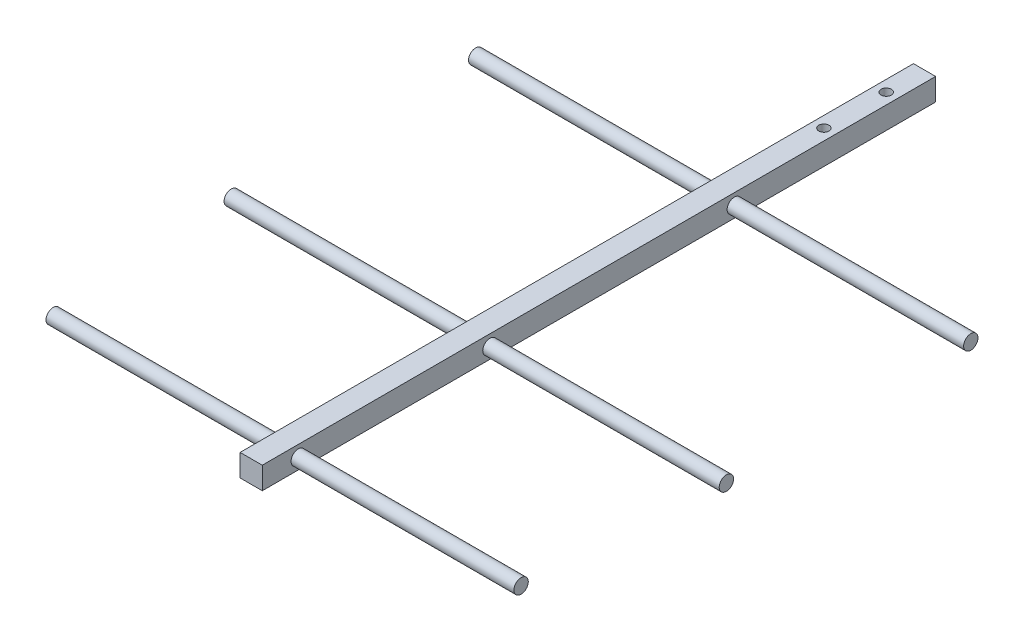
SolidWorks part; units mm, degrees
ref_plane "Front Plane" through (0, 0, 0) normal (0, 0, 1) x (1, 0, 0)
ref_plane "Top Plane" through (0, 0, 0) normal (0, 1, 0) x (1, 0, 0)
ref_plane "Right Plane" through (0, 0, 0) normal (1, 0, 0) x (0, 0, -1)
sketch "Sketch1" plane through (0, 0, 0) normal (0, 0, 1) x (1, 0, 0)
  line L1 (-7.3422, 7.3422) -> (7.3422, 7.3422)
  line L2 (-7.3422, 7.3422) -> (-7.3422, -7.3422)
  line L3 (-7.3422, -7.3422) -> (7.3422, -7.3422)
  line L4 (7.3422, 7.3422) -> (7.3422, -7.3422)
  line L5 (-7.3422, 7.3422) -> (7.3422, -7.3422) construction
  line L6 (-7.3422, -7.3422) -> (7.3422, 7.3422) construction
  point P0 (0, 0)
  dimension "D1" = 14.6844
  dimension "D2" = 14.6844
extrude "Boss-Extrude1" add sketch "Sketch1" along normal blind 446.0875
sketch "Sketch3" plane through (0, 0, 0) normal (1, 0, 0) x (0, 0, -1)
  line L0 (-446.0875, 0) -> (0, 0) construction
  line L1 (-446.0875, -7.3422) -> (-446.0875, 7.3422) construction
  line L2 (0, -7.3422) -> (0, 7.3422) construction
  circle A0 centre (-133.35, 0) radius 4.7625
  circle A1 centre (-295.275, 0) radius 4.7625
  circle A2 centre (-422.275, 0) radius 4.7625
  dimension "D1" = 9.525
  dimension "D2" = 127
  dimension "D3" = 288.925
  dimension "D4" = 23.8125
ref_plane "Plane1" through (37.3422, 0, 0) normal (1, 0, 0) x (0, 0, -1)
sketch "Sketch9" plane through (0, 7.3422, 0) normal (0, 1, 0) x (1, 0, 0)
  line L0 (0, 0) -> (0, -25.4) construction
  line L1 (0, -25.4) -> (0, -66.675) construction
  line L2 (7.3422, 0) -> (-7.3422, 0) construction
  circle A0 centre (0, -25.4) radius 3.3845
  circle A1 centre (0, -66.675) radius 3.3845
  dimension "D1" = 41.275
  dimension "D2" = 25.4
extrude "Cut-Extrude1" cut sketch "Sketch9" against normal through all
extrude "Boss-Extrude7" add sketch "Sketch3" along normal blind 155 and the other way blind 155 contours L0 A2 | A2 L0 region at (0, 2.0213, 422.275) region at (0, -2.0213, 422.275)
extrude "Boss-Extrude8" add sketch "Sketch3<3>" along normal blind 164 and the other way blind 164 contours L0 A0 | A0 L0 region at (0, 2.0213, 133.35) region at (0, -2.0213, 133.35)
sketch "Sketch3<3>" plane through (0, 0, 0) normal (1, 0, 0) x (0, 0, -1) same geometry as "Sketch3"
extrude "Boss-Extrude9" add sketch "Sketch3<4>" along normal blind 164 and the other way blind 164 contours A1 L0 | A1 region at (0, 2.0213, 295.275)
sketch "Sketch3<4>" plane through (0, 0, 0) normal (1, 0, 0) x (0, 0, -1) same geometry as "Sketch3"
ref_plane "Plane2" through (0, 0, 0) normal (0, 1, 0) x (1, 0, 0)
equation "\"D1@Sketch1\"=\"D2@Sketch1\""
